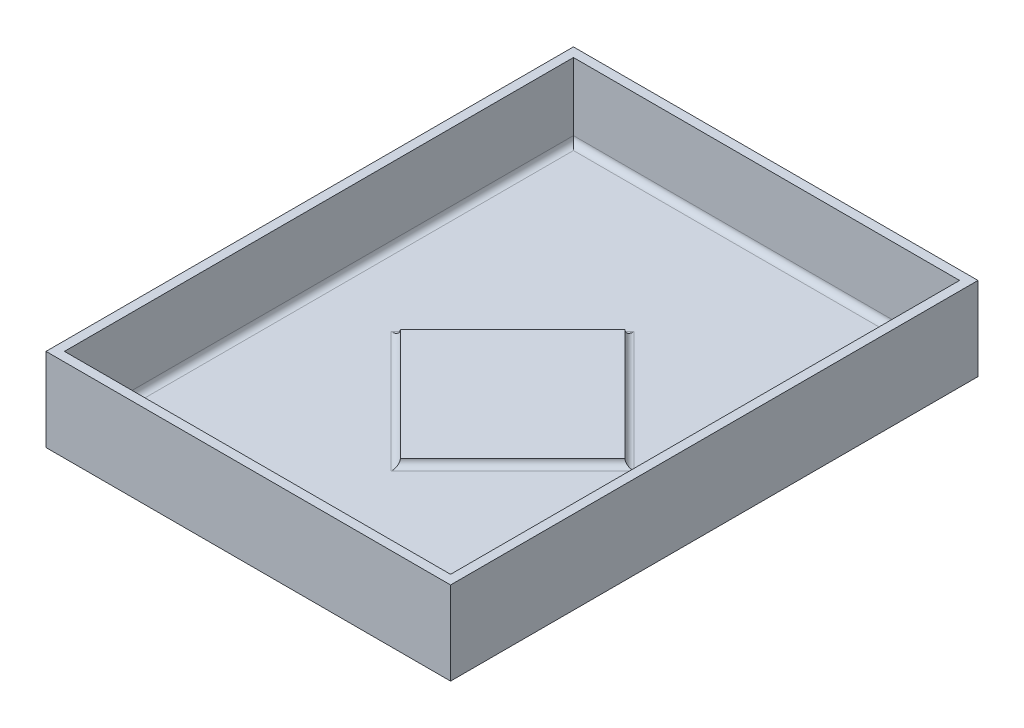
SolidWorks part; units mm, degrees
ref_plane "Front Plane" through (0, 0, 0) normal (0, 0, 1) x (1, 0, 0)
ref_plane "Top Plane" through (0, 0, 0) normal (0, 1, 0) x (1, 0, 0)
ref_plane "Right Plane" through (0, 0, 0) normal (1, 0, 0) x (0, 0, -1)
sketch "Sketch1" plane through (0, 0, 0) normal (0, 1, 0) x (1, 0, 0)
  line L0 (0, 276.225) -> (419.1, 276.225) construction
  line L1 (0, 0) -> (419.1, 0) construction
  line L2 (0, 0) -> (0, 552.45) construction
  line L3 (0, 552.45) -> (419.1, 552.45) construction
  line L4 (419.1, 0) -> (419.1, 552.45) construction
  line L5 (209.55, 154.9915) -> (330.7835, 276.225) construction
  line L6 (209.55, 154.9915) -> (88.3165, 276.225) construction
  line L7 (88.3165, 276.225) -> (209.55, 397.4585) construction
  line L8 (330.7835, 276.225) -> (209.55, 397.4585) construction
  line L9 (209.55, 397.4585) -> (209.55, 276.225) construction
  line L10 (209.55, 276.225) -> (209.55, 154.9915) construction
  line L13 (209.55, 0) -> (209.55, 154.9915) construction
  line L16 (209.55, 397.4585) -> (209.55, 552.45) construction
sketch "Sketch2" plane through (0, 0, 0) normal (0, 1, 0) x (1, 0, 0)
  line L1 (0, 552.45) -> (419.1, 552.45)
  line L2 (0, 552.45) -> (0, 0)
  line L3 (0, 0) -> (419.1, 0)
  line L4 (419.1, 552.45) -> (419.1, 0)
  line L5 (-10, 562.45) -> (429.1, 562.45)
  line L6 (-10, 562.45) -> (-10, -10)
  line L7 (-10, -10) -> (429.1, -10)
  line L8 (429.1, 562.45) -> (429.1, -10)
extrude "Boss-Extrude1" add sketch "Sketch2" along normal blind 80.42
sketch "Sketch3" plane through (0, 0, 0) normal (0, 1, 0) x (1, 0, 0)
  line L0 (88.3165, 276.225) -> (209.55, 154.9915)
  line L1 (88.3165, 276.225) -> (210.2221, 398.1306)
  line L2 (209.55, 154.9915) -> (331.4556, 276.8971)
  line L3 (210.2221, 398.1306) -> (331.4556, 276.8971)
extrude "Boss-Extrude2" add sketch "Sketch3" along normal blind 7.16 separate body
sketch "Sketch4" plane through (0, 0, 0) normal (0, 1, 0) x (1, 0, 0)
  line L1 (429.1, -10) -> (-10, -10)
  line L2 (429.1, -10) -> (429.1, 562.45)
  line L3 (429.1, 562.45) -> (-10, 562.45)
  line L4 (-10, -10) -> (-10, 562.45)
extrude "Boss-Extrude3" add sketch "Sketch4" against normal blind 10
fillet "Fillet1" radius 7 8 edges at (270.5028, 0, -215.9443) (270.8388, 0, -337.5138) (149.2693, 0, -337.1778) (148.9333, 0, -215.6083) (419.1, 0, -276.225) (209.55, 0, 0) (0, 0, -276.225) (209.55, 0, -552.45)
ref_axis "Axis1" through (209.55, 375.562, -276.225) along (0, -1, 0)
